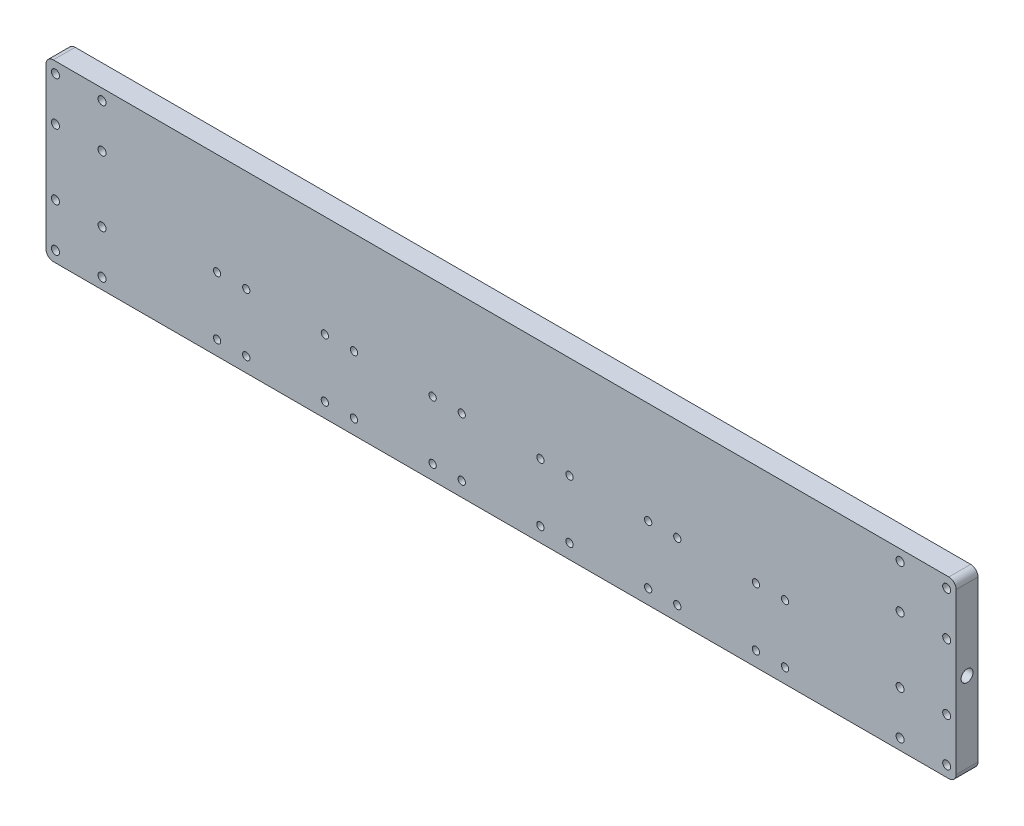
SolidWorks part; units mm, degrees
ref_plane "Plan de face" through (0, 0, 0) normal (0, 0, 1) x (1, 0, 0)
ref_plane "Plan de dessus" through (0, 0, 0) normal (0, 1, 0) x (1, 0, 0)
ref_plane "Plan de droite" through (0, 0, 0) normal (1, 0, 0) x (0, 0, -1)
sketch "Esquisse1" plane through (0, 0, 0) normal (0, 0, 1) x (1, 0, 0)
  line L1 (0, 0) -> (625, 0)
  line L2 (0, 0) -> (0, 120)
  line L3 (0, 120) -> (625, 120)
  line L4 (625, 0) -> (625, 120)
  dimension "D1" = 120
  dimension "D2" = 625
extrude "Boss.-Extru.1" add sketch "Esquisse1" along normal blind 15
sketch "Esquisse2" plane through (0, 0, 15) normal (0, 0, 1) x (1, 0, 0)
  line L0 (312.5, 0) -> (312.5, 120) construction
  line L1 (0, 0) -> (625, 0) construction
  line L2 (625, 120) -> (0, 120) construction
  line L3 (22.5, 120) -> (22.5, 0) construction
  line L4 (22.5, 60) -> (0, 60) construction
  line L5 (0, 120) -> (0, 0) construction
  line L6 (6.5, 112.5) -> (6.5, 82.5) construction
  line L7 (618.5, 112.5) -> (618.5, 82.5) construction
  line L8 (602.5, 60) -> (625, 60) construction
  line L9 (602.5, 120) -> (602.5, 0) construction
  circle A0 centre (6.5, 112.5) radius 2.75
  circle A1 centre (6.5, 82.5) radius 2.75
  circle A2 centre (38.5, 82.5) radius 2.75
  circle A3 centre (38.5, 112.5) radius 2.75
  circle A4 centre (38.5, 7.5) radius 2.75
  circle A5 centre (38.5, 37.5) radius 2.75
  circle A6 centre (6.5, 37.5) radius 2.75
  circle A7 centre (6.5, 7.5) radius 2.75
  circle A8 centre (618.5, 7.5) radius 2.75
  circle A9 centre (618.5, 37.5) radius 2.75
  circle A10 centre (586.5, 37.5) radius 2.75
  circle A11 centre (586.5, 7.5) radius 2.75
  circle A12 centre (586.5, 112.5) radius 2.75
  circle A13 centre (586.5, 82.5) radius 2.75
  circle A14 centre (618.5, 82.5) radius 2.75
  circle A15 centre (618.5, 112.5) radius 2.75
  dimension "D1" = 30
  dimension "D2" = 32
  dimension "D3" = 5.5
  dimension "D4" = 45
  dimension "D5" = 580
extrude "Enlèv. mat.-Extru.1" cut sketch "Esquisse2" against normal through all both and the other way through all
fillet "Congé1" radius 5 4 edges at (625, 120, 7.5) (625, 0, 7.5) (0, 0, 7.5) (0, 120, 7.5)
sketch "Esquisse3" plane through (625, 0, 0) normal (1, 0, 0) x (0, 0, -1)
  line L0 (-15, 60) -> (0, 60) construction
  line L1 (-15, 5) -> (-15, 115) construction
  line L2 (0, 5) -> (0, 115) construction
  circle A0 centre (-7.5, 60) radius 4.1
  dimension "D1" = 8.2
extrude "Enlèv. mat.-Extru.2" cut sketch "Esquisse3" against normal blind 20
extrude "Enlèv. mat.-Extru.3" cut sketch "Esquisse3<2>" along normal blind 20 from surface starting at face at (0, 60, 7.5)
sketch "Esquisse3<2>" plane through (625, 0, 0) normal (1, 0, 0) x (0, 0, -1) same geometry as "Esquisse3"
sketch "Esquisse4" plane through (0, 0, 15) normal (0, 0, 1) x (1, 0, 0)
  line L0 (0, 30) -> (625, 30) construction
  line L3 (312.5, 30) -> (312.5, 120) construction
  line L4 (620, 120) -> (5, 120) construction
  line L5 (275.5, 30) -> (275.5, 93.3675) construction
  line L6 (238.5, 30) -> (238.5, 112.952) construction
  line L7 (164.5, 30) -> (164.5, 101.3546) construction
  line L8 (0, 115) -> (0, 5) construction
  line L9 (5, 0) -> (620, 0) construction
  circle A0 centre (265.5, 50) radius 2.5
  circle A1 centre (285.5, 50) radius 2.5
  circle A2 centre (285.5, 10) radius 2.5
  circle A3 centre (265.5, 10) radius 2.5
  circle A4 centre (359.5, 10) radius 2.5
  circle A5 centre (339.5, 10) radius 2.5
  circle A6 centre (339.5, 50) radius 2.5
  circle A7 centre (359.5, 50) radius 2.5
  circle A8 centre (211.5, 10) radius 2.5
  circle A9 centre (191.5, 10) radius 2.5
  circle A10 centre (191.5, 50) radius 2.5
  circle A11 centre (211.5, 50) radius 2.5
  circle A12 centre (117.5, 50) radius 2.5
  circle A13 centre (137.5, 50) radius 2.5
  circle A14 centre (137.5, 10) radius 2.5
  circle A15 centre (117.5, 10) radius 2.5
  circle A16 centre (507.5, 10) radius 2.5
  circle A17 centre (487.5, 10) radius 2.5
  circle A18 centre (487.5, 50) radius 2.5
  circle A19 centre (507.5, 50) radius 2.5
  circle A20 centre (413.5, 50) radius 2.5
  circle A21 centre (433.5, 50) radius 2.5
  circle A22 centre (433.5, 10) radius 2.5
  circle A23 centre (413.5, 10) radius 2.5
  point P2 (0, 45.3873)
  point P4 (0, 0)
  point P64 (0, 0)
  point P65 (625, 50.5353)
  dimension "D1" = 5
  dimension "D2" = 20
  dimension "D3" = 40
  dimension "D4" = 37
  dimension "D5" = 74
  dimension "D6" = 74
  dimension "D7" = 30
extrude "Enlèv. mat.-Extru.4" cut sketch "Esquisse4" against normal through all both and the other way through all
